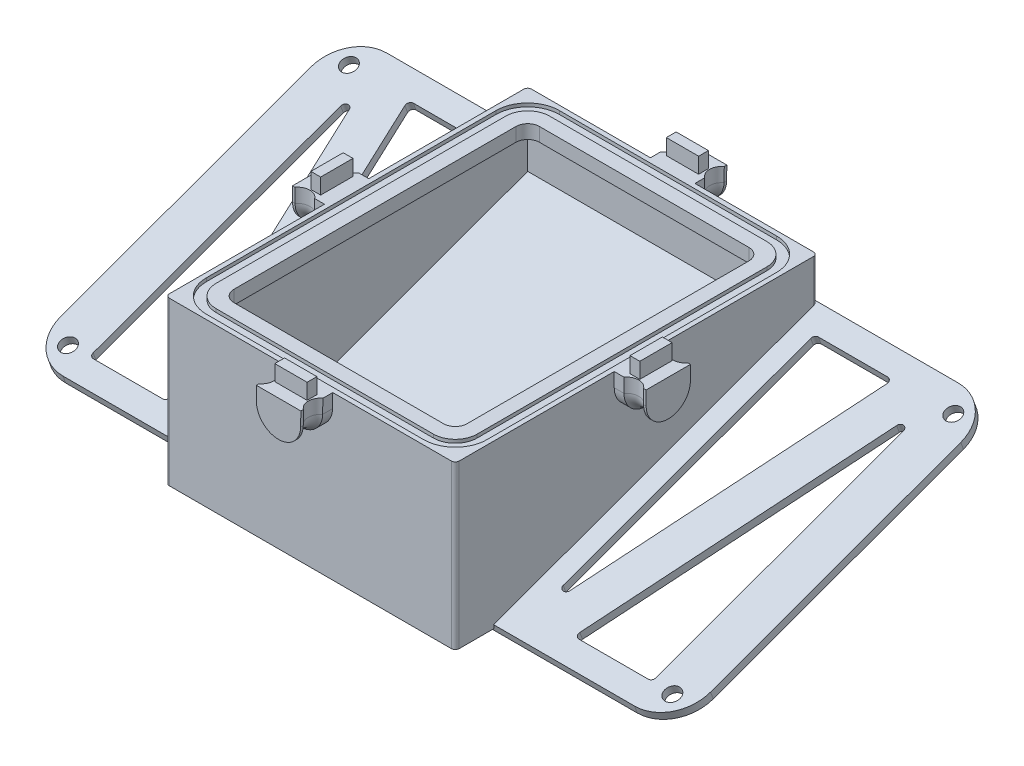
SolidWorks part; units mm, degrees
ref_plane "Front Plane" through (0, 0, 0) normal (0, 0, 1) x (1, 0, 0)
ref_plane "Top Plane" through (0, 0, 0) normal (0, 1, 0) x (1, 0, 0)
ref_plane "Right Plane" through (0, 0, 0) normal (1, 0, 0) x (0, 0, -1)
sketch "Sketch1" plane through (0, 0, 0) normal (0, 1, 0) x (1, 0, 0)
  line L1 (-39.4255, 34.2673) -> (54.5545, 34.2673)
  line L2 (-39.4255, 34.2673) -> (-39.4255, -83.1942)
  line L3 (-39.4255, -83.1942) -> (54.5545, -83.1942)
  line L4 (54.5545, 34.2673) -> (54.5545, -83.1942)
  dimension "D1" = 93.98
  dimension "D2" = 117.4615
extrude "Boss-Extrude1" add sketch "Sketch1" along normal blind 4.445
sketch "Sketch2" plane through (0, 4.445, 0) normal (0, 1, 0) x (1, 0, 0)
  line L0 (-33.8692, 28.711) -> (-33.8692, 34.2673)
  line L1 (-27.5192, 28.711) -> (42.6483, 28.711)
  line L2 (-33.8692, 22.361) -> (-33.8692, -71.288)
  line L3 (-27.5192, -77.638) -> (42.6483, -77.638)
  line L4 (48.9983, 22.361) -> (48.9983, -71.288)
  line L5 (54.5545, 34.2673) -> (-39.4255, 34.2673) construction
  line L6 (-33.8692, 28.711) -> (-39.4255, 28.711)
  line L7 (-39.4255, 34.2673) -> (-39.4255, -83.1942) construction
  line L8 (48.9983, -77.638) -> (54.5545, -77.638)
  line L9 (54.5545, -83.1942) -> (54.5545, 34.2673) construction
  line L10 (54.5545, -77.638) -> (48.9983, -77.638)
  line L11 (48.9983, -77.638) -> (48.9983, -83.1942)
  line L12 (-39.4255, -83.1942) -> (54.5545, -83.1942) construction
  arc A0 (42.6483, -77.638) -> (48.9983, -71.288) centre (42.6483, -71.288) ccw
  arc A1 (-33.8692, -71.288) -> (-27.5192, -77.638) centre (-27.5192, -71.288) ccw
  arc A2 (48.9983, 22.361) -> (42.6483, 28.711) centre (42.6483, 22.361) ccw
  arc A3 (-27.5192, 28.711) -> (-33.8692, 22.361) centre (-27.5192, 22.361) ccw
  dimension "D5" = 6.35
  dimension "D1" = 5.5562
  dimension "D2" = 5.5562
  dimension "D3" = 5.5562
  dimension "D4" = 5.5562
sketch "Sketch3" plane through (0, 4.445, 0) normal (0, 1, 0) x (1, 0, 0)
  line L0 (-36.0917, 30.9335) -> (-39.4255, 34.2673) construction
  line L1 (-32.8716, 30.9335) -> (48.0006, 30.9335)
  line L2 (-36.0917, 27.7134) -> (-36.0917, -76.6404)
  line L3 (7.5645, 34.2673) -> (7.5645, -83.1942) construction
  line L4 (-36.0917, 30.9335) -> (-36.0917, -76.6404) construction
  line L5 (-36.0917, -79.8605) -> (-36.0008, -79.8605) construction
  line L6 (51.2208, -79.8605) -> (51.2208, -79.7696) construction
  line L7 (51.2208, 30.9335) -> (51.1299, 30.9335) construction
  line L8 (-37.3617, -81.1305) -> (52.4908, -81.1305)
  line L9 (52.4908, -81.1305) -> (52.4908, 32.2035)
  line L10 (51.1299, -79.8605) -> (51.2208, -79.8605) construction
  line L11 (54.5545, 34.2673) -> (-39.4255, 34.2673) construction
  line L12 (-39.4255, -83.1942) -> (54.5545, -83.1942) construction
  line L13 (54.5545, -24.4635) -> (-39.4255, -24.4635) construction
  line L14 (-34.028, -77.7967) -> (49.157, -77.7967)
  line L15 (49.157, -77.7967) -> (49.157, 28.8698)
  line L16 (49.157, 28.8698) -> (-34.028, 28.8698)
  line L17 (-34.028, 28.8698) -> (-34.028, -77.7967)
  line L18 (-34.028, -77.7967) -> (49.157, -77.7967)
  line L19 (49.157, -77.7967) -> (49.157, 28.8698)
  line L20 (49.157, 28.8698) -> (-34.028, 28.8698)
  line L21 (-34.028, 28.8698) -> (-34.028, -77.7967)
  line L22 (54.5545, -83.1942) -> (54.5545, 34.2673) construction
  line L23 (-39.4255, 34.2673) -> (-39.4255, -83.1942) construction
  line L24 (-37.3617, -76.6404) -> (-37.3617, 27.7134)
  line L25 (48.0006, -81.1305) -> (-32.8716, -81.1305)
  line L26 (52.4908, 27.7134) -> (52.4908, -76.6404)
  line L27 (48.0006, 32.2035) -> (-32.8716, 32.2035)
  line L28 (52.4908, 32.2035) -> (-37.3617, 32.2035)
  line L29 (-37.3617, 32.2035) -> (-37.3617, -81.1305)
  line L30 (-37.3617, -81.1305) -> (52.4908, -81.1305) construction
  line L31 (52.4908, -81.1305) -> (52.4908, 32.2035) construction
  line L32 (52.4908, 32.2035) -> (-32.8716, 32.2035) construction
  line L33 (-37.3617, 27.7134) -> (-37.3617, -81.1305) construction
  line L34 (-36.0917, 30.9335) -> (-32.8716, 27.7134) construction
  line L35 (-32.8716, 27.7134) -> (-32.8716, 32.2035) construction
  line L36 (-32.8716, 27.7134) -> (-37.3617, 27.7134) construction
  line L37 (51.1299, 30.9335) -> (51.2208, 30.9335) construction
  line L38 (48.0006, 30.9335) -> (-36.0917, 30.9335) construction
  line L39 (51.2208, 30.9335) -> (-36.0917, 30.9335) construction
  line L40 (51.2208, 30.8426) -> (51.2208, 30.9335) construction
  line L41 (51.2208, -79.8605) -> (51.2208, 30.9335) construction
  line L42 (-36.0917, -79.8605) -> (51.2208, -79.8605) construction
  line L43 (51.2208, -76.6404) -> (51.2208, 27.7134)
  line L44 (-36.0917, -79.7696) -> (-36.0917, -79.8605) construction
  line L45 (-36.0917, -79.7696) -> (-36.0917, -79.8605) construction
  line L46 (-36.0917, 30.9335) -> (-36.0917, -79.8605) construction
  line L47 (-32.8716, -79.8605) -> (48.0006, -79.8605)
  arc A0 (-36.0917, 27.7134) -> (-32.8716, 30.9335) centre (-32.8716, 27.7134) cw
  arc A1 (-37.3617, 27.7134) -> (-32.8716, 32.2035) centre (-32.8716, 27.7134) cw
  arc A2 (51.2208, 27.7134) -> (48.0006, 30.9335) centre (48.0006, 27.7134) ccw
  arc A3 (52.4908, 27.7134) -> (48.0006, 32.2035) centre (48.0006, 27.7134) ccw
  arc A4 (51.2208, -76.6404) -> (48.0006, -79.8605) centre (48.0006, -76.6404) cw
  arc A5 (52.4908, -76.6404) -> (48.0006, -81.1305) centre (48.0006, -76.6404) cw
  arc A6 (-36.0917, -76.6404) -> (-32.8716, -79.8605) centre (-32.8716, -76.6404) ccw
  arc A7 (-37.3617, -76.6404) -> (-32.8716, -81.1305) centre (-32.8716, -76.6404) ccw
  dimension "D4" = 6.35
  dimension "D1" = 5.3975
  dimension "D2" = 2.0638
  dimension "D3" = 2.0638
sketch "Sketch7" plane through (-39.4255, 0, 0) normal (-1, 0, 0) x (0, 0, 1)
  line L0 (24.4635, 4.445) -> (24.4635, -0.127) construction
  line L1 (-34.2673, 4.445) -> (83.1942, 4.445) construction
  line L2 (17.288, -0.127) -> (31.639, -0.127) construction
  line L3 (31.639, -0.127) -> (31.639, 4.445)
  line L4 (17.288, -0.127) -> (17.288, 4.445)
  line L5 (31.639, 4.445) -> (17.288, 4.445)
  arc A0 (31.639, -0.127) -> (17.288, -0.127) centre (24.4635, -0.127) cw
  line M4 (-34.2673, 0) -> (83.1942, 0)
  line M6 (83.1942, 4.445) -> (-34.2673, 4.445)
  dimension "D1" = 7.1755
  dimension "D2" = 4.572
extrude "Boss-Extrude2" add sketch "Sketch7" along normal blind 10.3505 contours A0 M4 | A0 L3 L4 M6 M4
sketch "Sketch8" plane through (0, 4.445, 0) normal (0, 1, 0) x (1, 0, 0)
  line L0 (-39.4255, -31.639) -> (-39.4255, -17.288)
  line L1 (-39.4255, -24.4635) -> (-45.7755, -24.4635) construction
  line L2 (-45.7755, -24.4635) -> (-45.7755, -17.288) construction
  line L3 (-49.776, -17.288) -> (-39.4255, -17.288) construction
  line L4 (-45.7755, -24.4635) -> (-45.7755, -31.639) construction
  line L5 (-49.776, -31.639) -> (-39.4255, -31.639) construction
  line L6 (-45.7755, -31.639) -> (-48.9505, -31.639)
  line L7 (-45.7755, -31.639) -> (-42.6005, -31.639)
  line L8 (-45.7755, -17.288) -> (-48.9505, -17.288)
  line L9 (-45.7755, -17.288) -> (-42.6005, -17.288)
  line L10 (-45.7755, -17.288) -> (-45.7755, -18.8755) construction
  line L11 (-45.7755, -18.8755) -> (-49.776, -18.8755) construction
  line L12 (-49.776, -31.639) -> (-49.776, -17.288) construction
  line L13 (-45.7755, -18.8755) -> (-39.4255, -18.8755) construction
  line L14 (-45.7755, -31.639) -> (-45.7755, -30.0515) construction
  line L15 (-45.7755, -30.0515) -> (-49.776, -30.0515) construction
  line L16 (-45.7755, -30.0515) -> (-39.4255, -30.0515) construction
  arc A0 (-42.6005, -17.288) -> (-48.9505, -17.288) centre (-45.7755, -14.9067) cw
  arc A1 (-42.6005, -31.639) -> (-48.9505, -31.639) centre (-45.7755, -34.0202) ccw
  line M7 (-39.4255, -17.288) -> (-49.776, -17.288)
  line M9 (-49.776, -31.639) -> (-39.4255, -31.639)
  dimension "D1" = 6.35
  dimension "D2" = 3.175
  dimension "D3" = 3.175
  dimension "D4" = 3.175
  dimension "D5" = 3.175
  dimension "D6" = 1.5875
  dimension "D7" = 1.5875
extrude "Cut-Extrude3" cut sketch "Sketch8" against normal blind 4.572 contours A1 M9 | A0 M7
sketch "Sketch9" plane through (0, -0.127, 0) normal (0, 1, 0) x (1, 0, 0)
  line L0 (-45.7755, -31.639) -> (-45.7755, -24.4635) construction
  line L1 (-48.9505, -31.639) -> (-42.6005, -31.639) construction
  line L4 (-45.7755, -24.4635) -> (-46.0295, -24.4635) construction
  line L6 (-48.9505, -31.639) -> (-48.9505, -30.0515) construction
  line L7 (-48.9505, -30.0515) -> (-45.7755, -30.0515) construction
  line L9 (-45.7755, -30.0515) -> (-42.6005, -30.0515) construction
  line L12 (-42.6005, -30.0515) -> (-42.6005, -31.639) construction
  line L13 (-42.6005, -31.639) -> (-48.9505, -31.639)
  arc A0 (-42.6005, -31.639) -> (-48.9505, -31.639) centre (-45.7755, -34.0202) ccw
  arc A2 (-42.6005, -31.639) -> (-48.9505, -31.639) centre (-45.7755, -34.0202) ccw construction
  dimension "D1" = 7.1755
  dimension "D2" = 0.254
revolve "Cut-Revolve2" cut sketch "Sketch9" angle 180 about L4
sketch "Sketch17" plane through (0, 4.445, 0) normal (0, 1, 0) x (1, 0, 0)
  line L0 (-39.4255, -31.639) -> (-39.4255, -17.288) construction
  line L1 (-42.6005, -31.639) -> (-42.6005, -17.288) construction
  line L2 (-42.6005, -24.4635) -> (-42.6005, -29.7022)
  line L3 (-42.6005, -29.7022) -> (-45.7755, -29.7022)
  line L4 (-45.7755, -29.7022) -> (-45.7755, -24.4635)
  line L5 (-45.7755, -24.4635) -> (-45.7755, -19.2247)
  line L6 (-45.7755, -24.4635) -> (-42.6005, -24.4635) construction
  line L7 (-45.7755, -19.2247) -> (-42.6005, -19.2247)
  line L8 (-42.6005, -19.2247) -> (-42.6005, -24.4635)
  dimension "D1" = 5.2387
  dimension "D2" = 3.175
  dimension "D3" = 5.2387
  dimension "D4" = 5.2387
extrude "Boss-Extrude3" add sketch "Sketch17" along normal blind 5.08
ref_plane "Plane1" through (7.5645, 0, 0) normal (-1, 0, 0) x (0, 0, 1)
ref_plane "Plane2" through (-14.3199, 0, 14.3199) normal (-0.7071, 0, 0.7071) x (0.7071, 0, 0.7071)
mirror "Mirror1" about plane through (7.5645, 0, 0) normal (-1, 0, 0) of "Boss-Extrude2", "Cut-Extrude3", "Cut-Revolve2", "Boss-Extrude3"
ref_plane "Plane3" through (21.8844, 0, 21.8844) normal (0.7071, 0, 0.7071) x (0.7071, 0, -0.7071)
sketch "Sketch18" plane through (0, 0, 83.1942) normal (0, 0, 1) x (1, 0, 0)
  line L0 (-39.4255, 4.445) -> (54.5545, 4.445) construction
  line L2 (-39.4255, 0) -> (54.5545, 0) construction
  line L5 (14.7389, -0.1263) -> (14.8194, 4.445)
  line L6 (0.389, 0) -> (0.389, 4.445)
  line L7 (14.8194, 4.445) -> (0.389, 4.445)
  line L8 (54.5545, 4.445) -> (54.5545, 0) construction
  arc A0 (14.7389, -0.1263) -> (0.389, 0) centre (7.5645, 0) cw
  dimension "D2" = 7.1755
  dimension "D3" = 46.99
  dimension "D1" = 4.572
  dimension "D4" = 46.99
extrude "Boss-Extrude4" add sketch "Sketch18" along normal blind 10.3505
sketch "Sketch19" plane through (0, 4.445, 0) normal (0, 1, 0) x (1, 0, 0)
  line L0 (14.8194, -83.1942) -> (0.389, -83.1942) construction
  line L1 (7.6042, -83.1942) -> (7.6042, -89.5442) construction
  line L2 (7.6042, -89.5442) -> (0.389, -89.5442) construction
  line L3 (0.389, -93.5447) -> (0.389, -83.1942) construction
  line L4 (7.6042, -89.5442) -> (14.8194, -89.5442) construction
  line L5 (14.8194, -93.5447) -> (14.8194, -83.1942) construction
  line L6 (0.389, -89.5442) -> (0.389, -92.7192)
  line L7 (0.389, -89.5442) -> (0.389, -86.3692)
  line L8 (0.389, -89.5442) -> (1.9765, -89.5442) construction
  line L9 (1.9765, -89.5442) -> (1.9765, -93.5447) construction
  line L10 (14.8194, -93.5447) -> (0.389, -93.5447) construction
  line L11 (1.9765, -89.5442) -> (1.9765, -83.1942) construction
  line L12 (14.8194, -89.5442) -> (14.8194, -86.3692)
  line L13 (14.8194, -89.5442) -> (14.8194, -92.7192)
  arc A0 (0.389, -92.7192) -> (0.389, -86.3692) centre (-1.9922, -89.5442) ccw
  arc A1 (14.8194, -92.7192) -> (14.8194, -86.3692) centre (17.2006, -89.5442) cw
  dimension "D1" = 6.35
  dimension "D2" = 3.175
  dimension "D3" = 3.175
  dimension "D4" = 1.5875
extrude "Cut-Extrude4" cut sketch "Sketch19" against normal blind 4.572 and the other way blind 10
sketch "Sketch20" plane through (0, -0.127, 0) normal (0, 1, 0) x (1, 0, 0)
  line L0 (0.389, -92.7192) -> (0.389, -86.3692)
  line L1 (0.389, -89.5442) -> (1.9765, -89.5442) construction
  line L2 (1.9765, -89.5442) -> (1.9765, -92.7192) construction
  line L3 (1.9765, -89.5442) -> (1.9765, -86.3692) construction
  line L4 (0.389, -89.5442) -> (7.5645, -89.5442) construction
  line L5 (7.5645, -89.5442) -> (7.5645, -89.7982) construction
  arc A0 (0.3901, -92.7184) -> (0.3901, -86.3701) centre (-1.9922, -89.5442) ccw construction
  arc A1 (0.389, -92.7192) -> (0.389, -86.3692) centre (-1.9922, -89.5442) ccw
  dimension "D1" = 7.1755
  dimension "D2" = 0.254
revolve "Cut-Revolve3" cut sketch "Sketch20" angle 180 about L5
sketch "Sketch23" plane through (0, 4.445, 0) normal (0, 1, 0) x (1, 0, 0)
  line L0 (14.8194, -86.3692) -> (0.389, -86.3692) construction
  line L1 (7.6042, -86.3692) -> (7.6042, -89.5442) construction
  line L2 (12.8429, -89.5442) -> (2.3654, -89.5442)
  line L3 (2.3654, -89.5442) -> (2.3654, -86.3692)
  line L4 (2.3654, -86.3692) -> (12.8429, -86.3692)
  line L5 (12.8429, -89.5442) -> (12.8429, -86.3692)
  dimension "D1" = 3.175
  dimension "D2" = 5.2387
extrude "Boss-Extrude5" add sketch "Sketch23" along normal blind 5.08
ref_plane "Plane4" through (0, 0, 24.4635) normal (0, 0, 1) x (1, 0, 0)
fillet "Fillet4" radius 1.27 2 edges at (-39.4255, 2.2225, -34.2673) (54.5545, 2.2225, -34.2673)
mirror "Mirror2" about plane through (0, 0, 24.4635) normal (0, 0, 1) of "Boss-Extrude4", "Cut-Extrude4", "Cut-Revolve3", "Boss-Extrude5"
sketch "Sketch24" plane through (0, 4.445, 0) normal (0, 1, 0) x (1, 0, 0)
  line L4 (14.8194, 32.7592) -> (0.389, 32.7592)
  line L5 (-37.9174, -17.288) -> (-37.9174, -31.639)
  line L6 (-37.9174, 32.7592) -> (-37.9174, -17.288)
  line L7 (0.389, 32.7592) -> (-37.9174, 32.7592)
  line L8 (-37.9174, 22.5198) -> (-37.9174, -17.288)
  line L9 (0.389, 32.7592) -> (-27.678, 32.7592)
  line L10 (0.389, -81.6861) -> (14.8194, -81.6861)
  line L11 (53.0464, -31.639) -> (53.0464, -17.288)
  line L24 (42.807, 29.6159) -> (14.8194, 29.6159)
  line L25 (14.8194, 29.6159) -> (0.389, 29.6159)
  line L26 (0.389, 29.6159) -> (-27.678, 29.6159)
  line L27 (-34.7741, 22.5198) -> (-34.7741, -17.288)
  line L28 (-34.7741, -17.288) -> (-34.7741, -31.639)
  line L29 (53.0464, 32.7592) -> (14.8194, 32.7592)
  line L30 (53.0464, -17.288) -> (53.0464, 32.7592)
  line L31 (42.807, 32.7592) -> (14.8194, 32.7592)
  line L32 (53.0464, -17.288) -> (53.0464, 22.5198)
  line L33 (-34.7741, -31.639) -> (-34.7741, -71.4467)
  line L34 (-27.678, -78.5429) -> (0.389, -78.5429)
  line L35 (0.389, -78.5429) -> (14.8194, -78.5429)
  line L36 (14.8194, -78.5429) -> (42.807, -78.5429)
  line L37 (14.8194, -81.6861) -> (53.0464, -81.6861)
  line L38 (53.0464, -81.6861) -> (53.0464, -31.639)
  line L39 (14.8194, -81.6861) -> (42.807, -81.6861)
  line L40 (53.0464, -71.4467) -> (53.0464, -31.639)
  line L41 (49.9031, -71.4467) -> (49.9031, -31.639)
  line L42 (49.9031, -31.639) -> (49.9031, -17.288)
  line L45 (-37.9174, -31.639) -> (-37.9174, -81.6861)
  line L46 (-37.9174, -81.6861) -> (0.389, -81.6861)
  line L47 (-37.9174, -31.639) -> (-37.9174, -71.4467)
  line L48 (-27.678, -81.6861) -> (0.389, -81.6861)
  line L76 (49.9031, -17.288) -> (49.9031, 22.5198)
  arc A2 (53.0464, 22.5198) -> (42.807, 32.7592) centre (42.807, 22.5198) ccw
  arc A3 (-27.678, 32.7592) -> (-37.9174, 22.5198) centre (-27.678, 22.5198) ccw
  arc A4 (-37.9174, -71.4467) -> (-27.678, -81.6861) centre (-27.678, -71.4467) ccw
  arc A5 (42.807, -81.6861) -> (53.0464, -71.4467) centre (42.807, -71.4467) ccw
  arc A6 (49.9031, 22.5198) -> (42.807, 29.6159) centre (42.807, 22.5198) ccw
  arc A7 (-27.678, 29.6159) -> (-34.7741, 22.5198) centre (-27.678, 22.5198) ccw
  arc A8 (-34.7741, -71.4467) -> (-27.678, -78.5429) centre (-27.678, -71.4467) ccw
  arc A9 (42.807, -78.5429) -> (49.9031, -71.4467) centre (42.807, -71.4467) ccw
  dimension "D6" = 10.2394
  dimension "D7" = 10.2394
  dimension "D1" = 1.5081
  dimension "D2" = 1.5081
  dimension "D3" = 1.5081
  dimension "D4" = 1.5081
  dimension "D5" = 3.1432
extrude "Cut-Extrude5" cut sketch "Sketch24" against normal blind 1.1112
sketch "Sketch25" plane through (0, 0, 0) normal (0, -1, 0) x (1, 0, 0)
  line L0 (54.5545, -32.9973) -> (54.5545, -24.1073)
  line L1 (54.5545, 17.288) -> (54.5545, -32.9973) construction
  line L2 (54.5545, -24.1073) -> (44.3945, -24.1073)
  line L3 (44.3945, -24.1073) -> (44.3945, -34.2673)
  line L4 (53.2845, -34.2673) -> (14.7411, -34.2673) construction
  line L7 (54.5545, 31.639) -> (54.5545, 17.288) construction
  line L8 (54.5545, 24.4635) -> (-39.4255, 24.4635) construction
  line L9 (0.389, 83.1942) -> (14.7411, 83.1942) construction
  line L10 (7.5651, 83.1942) -> (7.5651, -34.2673) construction
  line L11 (53.2845, -34.2673) -> (44.3945, -34.2673)
  line L12 (54.5545, 81.9242) -> (54.5545, 73.0342)
  line L13 (54.5545, 73.0342) -> (44.3945, 73.0342)
  line L14 (44.3945, 73.0342) -> (44.3945, 83.1942)
  line L15 (53.2845, 83.1942) -> (44.3945, 83.1942)
  line L16 (-38.1544, 83.1942) -> (-29.2644, 83.1942)
  line L17 (-29.2644, 73.0342) -> (-29.2644, 83.1942)
  line L18 (-39.4244, 73.0342) -> (-29.2644, 73.0342)
  line L19 (-39.4244, 81.9242) -> (-39.4244, 73.0342)
  line L20 (-39.4244, -32.9973) -> (-39.4244, -24.1073)
  line L21 (-39.4244, -24.1073) -> (-29.2644, -24.1073)
  line L22 (-29.2644, -24.1073) -> (-29.2644, -34.2673)
  line L23 (-38.1544, -34.2673) -> (-29.2644, -34.2673)
  arc A0 (53.2845, -34.2673) -> (54.5545, -32.9973) centre (53.2845, -32.9973) ccw
  arc A1 (53.2845, -34.2673) -> (54.5545, -32.9973) centre (53.2845, -32.9973) ccw construction
  arc A2 (53.2845, 83.1942) -> (54.5545, 81.9242) centre (53.2845, 81.9242) cw
  arc A3 (-38.1544, 83.1942) -> (-39.4244, 81.9242) centre (-38.1544, 81.9242) ccw
  arc A4 (-38.1544, -34.2673) -> (-39.4244, -32.9973) centre (-38.1544, -32.9973) cw
  dimension "D1" = 10.16
  dimension "D2" = 10.16
sketch "Sketch28" plane through (0, 0, 0) normal (0, -1, 0) x (1, 0, 0)
  line L0 (53.2845, -34.2673) -> (46.9345, -34.2673)
  line L1 (53.2845, -34.2673) -> (14.7411, -34.2673) construction
  line L2 (46.9345, -34.2673) -> (46.9345, -26.6473)
  line L3 (46.9345, -26.6473) -> (54.5545, -26.6473)
  line L4 (54.5545, 17.288) -> (54.5545, -32.9973) construction
  line L5 (54.5545, -26.6473) -> (54.5545, -32.9973)
  line L6 (-39.4255, 17.288) -> (-39.4255, 31.639)
  line L7 (-39.4255, -32.9973) -> (-39.4255, 17.288) construction
  line L8 (-39.4255, 31.639) -> (54.5545, 31.639)
  line L9 (54.5545, 31.639) -> (54.5545, 17.288)
  line L10 (54.5545, 17.288) -> (-39.4255, 17.288)
  line L11 (-39.4255, 24.4635) -> (54.5545, 24.4635)
  line L12 (54.5545, 75.5742) -> (54.5545, 81.9242)
  line L13 (46.9345, 75.5742) -> (54.5545, 75.5742)
  line L14 (46.9345, 83.1942) -> (46.9345, 75.5742)
  line L15 (53.2845, 83.1942) -> (46.9345, 83.1942)
  line L16 (0.389, 83.1942) -> (14.7411, 83.1942)
  line L17 (14.7411, 83.1942) -> (14.7411, -34.2673)
  line L18 (14.7411, -34.2673) -> (0.389, -34.2673)
  line L19 (0.389, -34.2673) -> (0.389, 83.1942)
  line L20 (7.5651, 83.1942) -> (7.5651, -34.2673)
  line L21 (-39.4244, -26.6473) -> (-39.4244, -32.9973)
  line L22 (-31.8044, -26.6473) -> (-39.4244, -26.6473)
  line L23 (-31.8044, -34.2673) -> (-31.8044, -26.6473)
  line L24 (-38.1544, -34.2673) -> (-31.8044, -34.2673)
  line L25 (-39.4244, 75.5742) -> (-39.4244, 81.9242)
  line L26 (-31.8044, 75.5742) -> (-39.4244, 75.5742)
  line L27 (-31.8044, 83.1942) -> (-31.8044, 75.5742)
  line L28 (-38.1544, 83.1942) -> (-31.8044, 83.1942)
  line L29 (54.5545, 81.9242) -> (54.5545, 83.1942)
  line L30 (54.5545, 83.1942) -> (53.2845, 83.1942)
  line L31 (-38.1544, 83.1942) -> (-39.4255, 83.1942)
  line L32 (-39.4255, 83.1942) -> (-39.4244, 81.9242)
  arc A0 (54.5545, -32.9973) -> (53.2845, -34.2673) centre (53.2845, -32.9973) cw
  arc A1 (53.2845, -34.2673) -> (54.5545, -32.9973) centre (53.2845, -32.9973) ccw construction
  arc A2 (54.5545, 81.9242) -> (53.2845, 83.1942) centre (53.2845, 81.9242) ccw
  arc A3 (-39.4244, -32.9973) -> (-38.1544, -34.2673) centre (-38.1544, -32.9973) ccw
  arc A4 (-39.4244, 81.9242) -> (-38.1544, 83.1942) centre (-38.1544, 81.9242) cw
  line M21 (-38.1555, -34.2673) -> (0.389, -34.2673)
  line M25 (14.7411, -34.2673) -> (53.2845, -34.2673)
  arc M26 (53.2845, -34.2673) -> (54.5545, -32.9973) centre (53.2845, -32.9973) ccw
  line M27 (54.5545, -32.9973) -> (54.5545, 17.288)
  dimension "D1" = 7.62
  dimension "D2" = 7.62
extrude "Boss-Extrude11" add sketch "Sketch28" along normal blind 8.89 contours L3 L2 M25 M26 M27 | L21 A3 L23 L22 M21
ref_plane "Plane8" through (0, -18.8634, -6.8657) normal (0, -0.9397, -0.342) x (1, 0, 0)
sketch "Sketch30" plane through (0, -18.8634, -6.8657) normal (0, -0.9397, -0.342) x (1, 0, 0)
  line L0 (-38.1555, -29.1602) -> (53.2845, -29.1602)
  line L1 (53.2845, -29.1602) -> (53.2845, 82.5998)
  line L2 (53.2845, 82.5998) -> (-38.1555, 82.5998)
  line L3 (-38.1555, 82.5998) -> (-38.1555, -29.1602)
  line L4 (53.2845, -29.1602) -> (112.9745, -29.1602)
  line L5 (112.9745, -29.1602) -> (112.9745, 82.5998)
  line L6 (112.9745, 82.5998) -> (53.2845, 82.5998)
  line L7 (-38.1555, -29.1602) -> (-97.8455, -29.1602)
  line L8 (-97.8455, -29.1602) -> (-97.8455, 82.5998)
  line L9 (-97.8455, 82.5998) -> (-38.1555, 82.5998)
  dimension "D1" = 111.76
  dimension "D2" = 59.69
  dimension "D3" = 59.69
extrude "Boss-Extrude12" add sketch "Sketch30" along normal blind 2.54 separate body contours L9 L8 L7 L3 | L2 L3 L0 L1 | L5 L6 L1 L4
sketch "Sketch31" plane through (0, -18.8634, -6.8657) normal (0, 0.9397, 0.342) x (1, 0, 0)
  line L0 (46.9345, 29.1602) -> (46.9345, -82.5998)
  line L1 (-97.8455, -82.5998) -> (112.9745, -82.5998) construction
  line L2 (46.9345, -82.5998) -> (54.5545, -82.5998)
  line L3 (54.5545, -82.5998) -> (54.5545, -74.9798)
  line L4 (54.5545, -74.9798) -> (46.9345, -74.9798)
  dimension "D1" = 7.62
  dimension "D2" = 7.62
sketch "Sketch34" plane through (0, -8.89, 0) normal (0, -1, 0) x (1, 0, 0)
  line L0 (-31.8044, -26.6473) -> (-39.4244, -26.6473)
  line L1 (-39.4244, -26.6473) -> (-39.4244, -32.9973)
  line L2 (-31.8044, -26.6473) -> (-31.8044, -34.2673)
  line L3 (-31.8044, -34.2673) -> (-38.1555, -34.2673)
  line L4 (46.9345, -26.6473) -> (46.9345, -34.2673)
  line L5 (46.9345, -34.2673) -> (53.2845, -34.2673)
  line L6 (46.9345, -26.6473) -> (54.5545, -26.6473)
  line L7 (54.5545, -26.6473) -> (54.5545, -32.9973)
  arc A0 (-38.1555, -34.2673) -> (-39.4244, -32.9973) centre (-38.1544, -32.9973) cw
  arc A1 (-39.4244, -32.9973) -> (-38.1555, -34.2673) centre (-38.1544, -32.9973) ccw construction
  arc A2 (54.5545, -32.9973) -> (53.2845, -34.2673) centre (53.2845, -32.9973) cw
  arc A3 (53.2845, -34.2673) -> (54.5545, -32.9973) centre (53.2845, -32.9973) ccw construction
extrude "Boss-Extrude19" add sketch "Sketch34" along normal up to surface contours A2 L7 L6 L4 L5
sketch "Sketch36" plane through (0, 0, 0) normal (0, -1, 0) x (1, 0, 0)
  line L0 (-31.8044, -34.2673) -> (-31.8044, 70.6347)
  line L1 (-31.8044, 70.6347) -> (-39.4255, 70.6347)
  line L2 (-39.4255, 31.639) -> (-39.4255, 83.1942) construction
  line L3 (-39.4255, 70.6347) -> (-39.4255, 63.0147)
  line L4 (-39.4255, 63.0147) -> (-31.8044, 63.0147)
  line L5 (-31.8044, 63.0147) -> (-31.8044, 70.6347)
  line L6 (0.389, 83.1942) -> (14.7411, 83.1942)
  line L7 (7.5651, 83.1942) -> (7.5651, -34.2673)
  line L8 (46.9345, 63.0147) -> (46.9345, 70.6347)
  line L9 (54.5556, 63.0147) -> (46.9345, 63.0147)
  line L10 (54.5556, 70.6347) -> (54.5556, 63.0147)
  line L11 (46.9345, 70.6347) -> (54.5556, 70.6347)
  line M22 (54.5545, 31.639) -> (54.5545, 83.1942)
  line M28 (-39.4255, 83.1942) -> (-39.4255, 31.639)
  dimension "D1" = 104.902
  dimension "D2" = 7.62
extrude "Boss-Extrude20" add sketch "Sketch36" along normal up to surface (47.0712 mm away) contours L4 L0 L1 M28 | L11 L8 L9 M22
sketch "Sketch37" plane through (0, -21.2502, -7.7344) normal (0, -0.9397, -0.342) x (1, 0, 0)
  line L0 (-97.8455, 82.5998) -> (-90.4455, 82.5998)
  line L1 (-97.8455, 82.5998) -> (112.9745, 82.5998) construction
  line L2 (-90.4455, 82.5998) -> (-90.4455, 75.1998)
  line L3 (-97.8455, 26.7198) -> (112.9745, 26.7198)
  line L4 (-97.8455, -29.1602) -> (-97.8455, 82.5998) construction
  line L5 (112.9745, -29.1602) -> (112.9745, 82.5998) construction
  line L6 (7.5645, -29.1602) -> (7.5645, 82.5998)
  line L7 (112.9745, -29.1602) -> (-97.8455, -29.1602) construction
  circle A0 centre (-90.4455, 75.1998) radius 2.4765
  circle A1 centre (-90.4455, -21.7602) radius 2.4765
  circle A2 centre (105.5745, -21.7602) radius 2.4765
  circle A3 centre (105.5745, 75.1998) radius 2.4765
  point P23 (0, 0)
  point P24 (0, 0)
  point P25 (0, 0)
  dimension "D3" = 4.953
  dimension "D1" = 7.4
  dimension "D2" = 7.4
extrude "Cut-Extrude6" cut sketch "Sketch37" against normal blind 25.4 contours A0 | A1 | A3 | A2
fillet "Fillet7" radius 12.7 4 edges at (112.9745, -48.3076, 70.3184) (112.9745, -10.0834, -34.7017) (-97.8455, -10.0834, -34.7017) (-97.8455, -48.3076, 70.3184)
sketch "Sketch39" plane through (0, -21.2502, -7.7344) normal (0, -0.9397, -0.342) x (-1, 0, 0)
  line L0 (37.9845, -82.5998) -> (45.6045, -82.5998)
  line L1 (85.1455, -82.5998) -> (-100.2745, -82.5998) construction
  line L2 (45.6045, -82.5998) -> (45.6045, -74.9798)
  line L3 (45.6045, -74.9798) -> (45.6045, 21.5402)
  line L4 (45.6045, 21.5402) -> (71.0045, 21.5402)
  line L6 (71.0045, 21.5402) -> (83.7045, 21.5402)
  line L7 (83.7045, 21.5402) -> (83.7045, -74.9798)
  line L8 (83.7045, -74.9798) -> (58.3045, -74.9798)
  line L9 (58.3045, -74.9798) -> (83.7045, 21.5402)
  line L10 (71.0045, 21.5402) -> (45.6045, -74.9798)
  line L11 (-7.5645, -82.5998) -> (-7.5645, 29.1602)
  line L12 (-100.2745, 29.1602) -> (85.1455, 29.1602) construction
  line L13 (-60.7335, 21.5402) -> (-86.1335, 21.5402)
  line L14 (-60.7335, -74.9798) -> (-60.7335, 21.5402)
  line L15 (-86.1335, 21.5402) -> (-60.7335, -74.9798)
  line L16 (-98.8335, -74.9798) -> (-73.4335, -74.9798)
  line L17 (-73.4335, -74.9798) -> (-98.8335, 21.5402)
  line L18 (-98.8335, 21.5402) -> (-98.8335, -74.9798)
  dimension "D1" = 7.62
  dimension "D2" = 7.62
  dimension "D3" = 96.52
  dimension "D4" = 25.4
  dimension "D5" = 12.7
  dimension "D6" = 25.4
  dimension "D7" = 45.549
extrude "Cut-Extrude7" cut sketch "Sketch39" against normal blind 10.16 contours L9 L8 L7 | L10 L4 L3 | L13 L15 L14 | L17 L18 L16
fillet "Fillet8" radius 1.27 12 edges at (60.7335, -45.7014, 63.1579) (98.8335, -45.7014, 63.1579) (86.1335, -12.6896, -27.5412) (98.8335, -12.6896, -27.5412) (60.7335, -12.6896, -27.5412) (-71.0045, -12.6896, -27.5412) (-45.6045, -12.6896, -27.5412) (-45.6045, -45.7014, 63.1579) (-83.7045, -12.6896, -27.5412) (-58.3045, -45.7014, 63.1579) (73.4335, -45.7014, 63.1579) (-83.7045, -45.7014, 63.1579)
sketch "Sketch41" plane through (0, 0, 0) normal (0, -1, 0) x (1, 0, 0)
  line L0 (54.5545, -26.6473) -> (54.5545, 63.0147)
  line L1 (54.5545, 63.0147) -> (46.9345, 63.0147)
  line L2 (46.9345, 63.0147) -> (46.9345, -26.6473)
  line L3 (46.9345, -26.6473) -> (-31.8044, -26.6473)
  line L4 (-31.8044, -26.6473) -> (-31.8044, -34.2673)
  line L5 (-31.8044, -34.2673) -> (46.9345, -34.2673)
  line L6 (46.9345, -34.2673) -> (46.9345, -26.6473)
  line L7 (54.5545, -26.6473) -> (46.9345, -26.6473)
  line L8 (-31.8044, -26.6473) -> (-39.4244, -26.6473)
  line L9 (-39.4244, -26.6473) -> (-39.4255, 63.0147)
  line L10 (-39.4255, 63.0147) -> (-31.8044, 63.0147)
  line L11 (-31.8044, 63.0147) -> (-31.8044, -26.6473)
  line M12 (-31.8044, 63.0147) -> (-39.4255, 63.0147)
  line M21 (-39.4244, -26.6473) -> (-31.8044, -26.6473)
  line M22 (-31.8044, -26.6473) -> (-31.8044, -34.2673)
  line M23 (-31.8044, -34.2673) -> (0.389, -34.2673)
  line M27 (14.7411, -34.2673) -> (46.9345, -34.2673)
  line M28 (46.9345, -34.2673) -> (46.9345, -26.6473)
  line M29 (46.9345, -26.6473) -> (54.5545, -26.6473)
  line M30 (54.5545, -26.6473) -> (54.5545, 17.288)
  line M34 (54.5545, 31.639) -> (54.5545, 63.0147)
  line M35 (54.5545, 63.0147) -> (46.9345, 63.0147)
  line M50 (0.389, -34.2673) -> (14.7411, -34.2673)
  line M51 (54.5545, 17.288) -> (54.5545, 31.639)
extrude "Boss-Extrude21" add sketch "Sketch41" along normal up to surface (11.6635 mm away) contours L2 M35 M29 M30 M51 M34 | L3 M28 M22 M23 M50 M27 | L11 L9 M12 M21
sketch "Sketch42" plane through (0, 0, 0) normal (0, -1, 0) x (1, 0, 0)
  line L0 (54.5545, 70.6347) -> (54.5545, 83.1942)
  line L2 (54.5545, 83.1942) -> (46.9345, 83.1942)
  line L3 (14.7411, 83.1942) -> (54.5545, 83.1942) construction
  line L4 (46.9345, 83.1942) -> (46.9345, 70.6347)
  line L5 (54.5545, 70.6347) -> (46.9345, 70.6347)
  line L6 (-31.8044, 70.6347) -> (-31.8044, 83.1942)
  line L7 (-39.4255, 83.1942) -> (0.389, 83.1942) construction
  line L8 (-31.8044, 83.1942) -> (-39.4255, 83.1942)
  line L9 (-39.4255, 83.1942) -> (-39.4255, 70.6347)
  line L10 (-39.4255, 70.6347) -> (-31.8044, 70.6347)
  line L11 (46.9345, 83.1942) -> (-31.8044, 83.1942)
  line L12 (46.9345, 83.1942) -> (46.9345, 75.5742)
  line L13 (46.9345, 75.5742) -> (-31.8044, 75.5742)
  line L14 (-31.8044, 83.1942) -> (-31.8044, 75.5742)
  line L15 (46.9345, 83.1942) -> (46.9345, 75.5742)
  line M8 (46.9345, 70.6347) -> (54.5545, 70.6347)
  line M9 (54.5545, 70.6347) -> (54.5545, 83.1942)
  line M10 (54.5545, 83.1942) -> (14.7411, 83.1942)
  line M11 (14.7411, 83.1942) -> (0.389, 83.1942)
  line M12 (0.389, 83.1942) -> (-39.4255, 83.1942)
  line M13 (-39.4255, 83.1942) -> (-39.4255, 70.6347)
  line M14 (-39.4255, 70.6347) -> (-31.8044, 70.6347)
  dimension "D1" = 7.62
extrude "Boss-Extrude22" add sketch "Sketch42" along normal blind 48.26 contours L4 M10 M8 M9 | L13 L4 L6 M10 M11 M12 | L6 M14 M12 M13
sketch "Sketch43" plane through (0, 0, 75.5742) normal (0, 0, -1) x (-1, 0, 0)
  line L0 (-46.9345, -48.26) -> (-46.9345, -44.456)
  line L1 (-46.9345, -48.26) -> (-46.9345, 0) construction
  line L2 (-46.9345, -44.456) -> (31.8044, -44.456)
  line L3 (31.8044, -48.26) -> (31.8044, 0) construction
  line L4 (31.8044, -44.456) -> (31.8044, -48.26)
  line L5 (31.8044, -48.26) -> (-46.9345, -48.26)
extrude "Boss-Extrude23" add sketch "Sketch43" along normal blind 7.62
sketch "Sketch44" plane through (0, 4.445, 0) normal (0, 1, 0) x (1, 0, 0)
  line L0 (-34.7741, -71.4467) -> (-27.678, -71.4467)
  line L1 (-27.678, 22.5198) -> (-27.678, -71.4467)
  line L2 (42.807, -71.4467) -> (-27.678, -71.4467)
  line L3 (-27.678, 22.5198) -> (42.807, 22.5198)
  line L4 (42.807, 22.5198) -> (42.807, -71.4467)
  line L5 (45.347, -73.9867) -> (-30.218, -73.9867)
  line L6 (45.347, 25.0598) -> (45.347, -73.9867)
  line L7 (-30.218, 25.0598) -> (45.347, 25.0598)
  line L8 (-30.218, 25.0598) -> (-30.218, -73.9867)
  dimension "D1" = 2.54
extrude "Cut-Extrude8" cut sketch "Sketch44" against normal blind 7.62
fillet "Fillet9" radius 3.81 4 edges at (45.347, 2.2225, 73.9867) (45.347, 2.2225, -25.0598) (-30.218, 2.2225, -25.0598) (-30.218, 2.2225, 73.9867)
fillet "Fillet10" radius 1.27 2 edges at (-39.4255, -21.9075, 83.1942) (54.5545, -21.9075, 83.1942)
